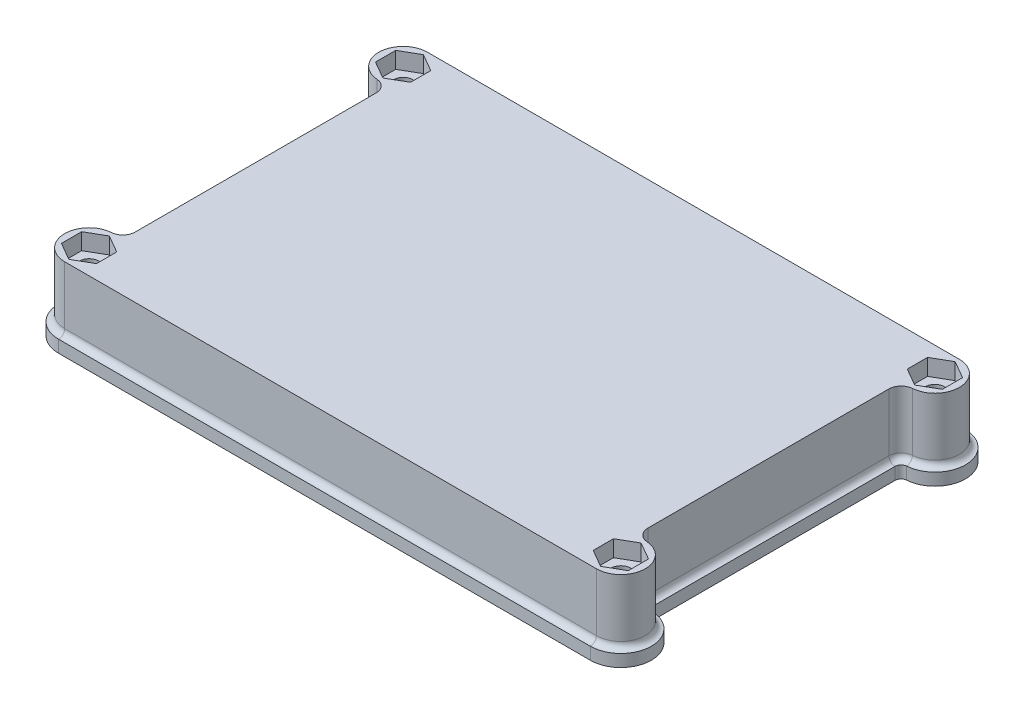
SolidWorks part; units mm, degrees
ref_plane "Спереди" through (0, 0, 0) normal (0, 0, 1) x (1, 0, 0)
ref_plane "Сверху" through (0, 0, 0) normal (0, 1, 0) x (1, 0, 0)
ref_plane "Справа" through (0, 0, 0) normal (1, 0, 0) x (0, 0, -1)
sketch "Эскиз1" plane through (0, 0, 0) normal (0, 1, 0) x (1, 0, 0)
  line L0 (38.2426, -23.75) -> (38.2426, 23.75)
  line L1 (35.2426, -26.75) -> (-36.8302, -26.75)
  line L2 (-42.8302, 19.7659) -> (-42.8302, -19.7659)
  line L3 (41.2426, 19.7659) -> (41.2426, -19.7659)
  line L5 (-39.8302, 23.75) -> (-39.8302, -23.75)
  line L6 (35.2426, 26.75) -> (-36.8302, 26.75)
  line L7 (-44.3938, -29.75) -> (42.8062, -29.75)
  line L10 (42.8062, 29.75) -> (-44.3938, 29.75)
  line L11 (-42.7938, 29.75) -> (41.2062, 29.75)
  line L12 (-42.7938, 0) -> (41.2062, 0) construction
  arc A0 (38.2426, 23.75) -> (35.2426, 26.75) centre (35.2426, 23.75) ccw
  arc A1 (-36.8302, -26.75) -> (-39.8302, -23.75) centre (-36.8302, -23.75) cw
  arc A2 (38.2426, -23.75) -> (35.2426, -26.75) centre (35.2426, -23.75) cw
  arc A3 (-36.8302, 26.75) -> (-39.8302, 23.75) centre (-36.8302, 23.75) ccw
  circle A4 centre (-44.3938, -25.75) radius 1.6
  arc A5 (-44.6847, -21.7606) -> (-44.3938, -29.75) centre (-44.3938, -25.75) ccw
  arc A6 (-44.6847, -21.7606) -> (-42.8302, -19.7659) centre (-44.8302, -19.7659) ccw
  circle A7 centre (-44.3938, 25.75) radius 1.6
  circle A8 centre (42.8062, 25.75) radius 1.6
  circle A9 centre (42.8062, -25.75) radius 1.6
  arc A10 (42.8062, -29.75) -> (43.0971, -21.7606) centre (42.8062, -25.75) ccw
  arc A11 (41.2426, -19.7659) -> (43.0971, -21.7606) centre (43.2426, -19.7659) ccw
  arc A12 (43.0971, 21.7606) -> (41.2426, 19.7659) centre (43.2426, 19.7659) ccw
  arc A13 (43.0971, 21.7606) -> (42.8062, 29.75) centre (42.8062, 25.75) ccw
  arc A14 (-42.8302, 19.7659) -> (-44.6847, 21.7606) centre (-44.8302, 19.7659) ccw
  arc A15 (-44.3938, 29.75) -> (-44.6847, 21.7606) centre (-44.3938, 25.75) ccw
extrude "Бобышка-Вытянуть1" add sketch "Эскиз1" along normal blind 9.5 contours L10 A15 A14 L2 A6 A5 L7 A10 A11 L3 A12 A13 A3 L6 A0 L0 A2 L1 A1 L5 A4 A7 A8 A9 region at (-42.5432, 0, -21.8921)
sketch "Эскиз2" plane through (0, 9.5, 0) normal (0, 1, 0) x (1, 0, 0)
  line L0 (41.2426, 19.7659) -> (41.2426, -19.7659) construction
  line L1 (-44.3938, -29.75) -> (42.8062, -29.75) construction
  line L2 (-42.8302, 19.7659) -> (-42.8302, -19.7659) construction
  line L3 (42.8062, 29.75) -> (-44.3938, 29.75) construction
  line L4 (41.2426, 19.7659) -> (41.2426, -19.7659)
  line L5 (-44.3938, -29.75) -> (42.8062, -29.75)
  line L6 (-42.8302, 19.7659) -> (-42.8302, -19.7659)
  line L7 (42.8062, 29.75) -> (-44.3938, 29.75)
  circle A0 centre (42.8062, 25.75) radius 1.6 construction
  arc A1 (43.0971, 21.7606) -> (42.8062, 29.75) centre (42.8062, 25.75) ccw construction
  arc A2 (43.0971, 21.7606) -> (41.2426, 19.7659) centre (43.2426, 19.7659) ccw construction
  arc A3 (41.2426, -19.7659) -> (43.0971, -21.7606) centre (43.2426, -19.7659) ccw construction
  circle A4 centre (42.8062, -25.75) radius 1.6 construction
  arc A5 (42.8062, -29.75) -> (43.0971, -21.7606) centre (42.8062, -25.75) ccw construction
  circle A6 centre (-44.3938, -25.75) radius 1.6 construction
  arc A7 (-44.6847, -21.7606) -> (-44.3938, -29.75) centre (-44.3938, -25.75) ccw construction
  arc A8 (-44.6847, -21.7606) -> (-42.8302, -19.7659) centre (-44.8302, -19.7659) ccw construction
  circle A9 centre (-44.3938, 25.75) radius 1.6 construction
  arc A10 (-42.8302, 19.7659) -> (-44.6847, 21.7606) centre (-44.8302, 19.7659) ccw construction
  arc A11 (-44.3938, 29.75) -> (-44.6847, 21.7606) centre (-44.3938, 25.75) ccw construction
  circle A12 centre (42.8062, 25.75) radius 1.6
  arc A13 (43.0971, 21.7606) -> (42.8062, 29.75) centre (42.8062, 25.75) ccw
  arc A14 (43.0971, 21.7606) -> (41.2426, 19.7659) centre (43.2426, 19.7659) ccw
  arc A15 (41.2426, -19.7659) -> (43.0971, -21.7606) centre (43.2426, -19.7659) ccw
  circle A16 centre (42.8062, -25.75) radius 1.6
  arc A17 (42.8062, -29.75) -> (43.0971, -21.7606) centre (42.8062, -25.75) ccw
  circle A18 centre (-44.3938, -25.75) radius 1.6
  arc A19 (-44.6847, -21.7606) -> (-44.3938, -29.75) centre (-44.3938, -25.75) ccw
  arc A20 (-44.6847, -21.7606) -> (-42.8302, -19.7659) centre (-44.8302, -19.7659) ccw
  circle A21 centre (-44.3938, 25.75) radius 1.6
  arc A22 (-42.8302, 19.7659) -> (-44.6847, 21.7606) centre (-44.8302, 19.7659) ccw
  arc A23 (-44.3938, 29.75) -> (-44.6847, 21.7606) centre (-44.3938, 25.75) ccw
extrude "Бобышка-Вытянуть2" add sketch "Эскиз2" along normal blind 2
sketch "Эскиз3" plane through (0, 11.5, 0) normal (0, 1, 0) x (1, 0, 0)
  line L0 (-0.7938, 29.75) -> (-0.7938, -29.75) construction
  line L1 (-44.3938, 22.4302) -> (-41.5188, 24.0901)
  line L2 (-41.5188, 24.0901) -> (-41.5188, 27.4099)
  line L3 (-41.5188, 27.4099) -> (-44.3938, 29.0698)
  line L4 (-44.3938, 29.0698) -> (-47.2688, 27.4099)
  line L5 (-47.2688, 27.4099) -> (-47.2688, 24.0901)
  line L6 (-47.2688, 24.0901) -> (-44.3938, 22.4302)
  line L7 (42.8062, 29.75) -> (-44.3938, 29.75) construction
  line L8 (-44.3938, -29.75) -> (42.8062, -29.75) construction
  line L9 (-42.8302, 0) -> (41.2426, 0) construction
  line L10 (-42.8302, 19.7659) -> (-42.8302, -19.7659) construction
  line L11 (41.2426, -19.7659) -> (41.2426, 19.7659) construction
  line L12 (45.6812, 24.0901) -> (42.8062, 22.4302)
  line L13 (45.6812, 27.4099) -> (45.6812, 24.0901)
  line L14 (42.8062, 29.0698) -> (45.6812, 27.4099)
  line L15 (39.9312, 27.4099) -> (42.8062, 29.0698)
  line L16 (39.9312, 24.0901) -> (39.9312, 27.4099)
  line L17 (42.8062, 22.4302) -> (39.9312, 24.0901)
  line L18 (42.8062, -22.4302) -> (39.9312, -24.0901)
  line L19 (39.9312, -24.0901) -> (39.9312, -27.4099)
  line L20 (39.9312, -27.4099) -> (42.8062, -29.0698)
  line L21 (42.8062, -29.0698) -> (45.6812, -27.4099)
  line L22 (45.6812, -27.4099) -> (45.6812, -24.0901)
  line L23 (45.6812, -24.0901) -> (42.8062, -22.4302)
  line L24 (-47.2688, -24.0901) -> (-44.3938, -22.4302)
  line L25 (-47.2688, -27.4099) -> (-47.2688, -24.0901)
  line L26 (-44.3938, -29.0698) -> (-47.2688, -27.4099)
  line L27 (-41.5188, -27.4099) -> (-44.3938, -29.0698)
  line L28 (-41.5188, -24.0901) -> (-41.5188, -27.4099)
  line L29 (-44.3938, -22.4302) -> (-41.5188, -24.0901)
  circle A0 centre (-44.3938, 25.75) radius 2.875 construction
  circle A1 centre (42.8062, 25.75) radius 2.875 construction
  circle A2 centre (42.8062, -25.75) radius 2.875 construction
  circle A3 centre (-44.3938, -25.75) radius 2.875 construction
extrude "Вырез-Вытянуть1" cut sketch "Эскиз3" against normal blind 2.7
sketch "Эскиз4" plane through (0, 0, 0) normal (0, -1, 0) x (1, 0, 0)
  line L0 (-0.7938, 26.75) -> (-0.7938, -26.75) construction
  line L1 (35.2426, 26.75) -> (-36.8302, 26.75) construction
  line L2 (35.2426, -26.75) -> (-36.8302, -26.75) construction
  line L3 (-39.8302, -23.75) -> (-39.8302, 23.75) construction
  line L4 (36.7426, -28.25) -> (-38.3302, -28.25)
  line L5 (39.7426, -25.25) -> (39.7426, 25.25)
  line L6 (36.7426, 28.25) -> (-38.3302, 28.25)
  line L7 (-41.3302, -25.25) -> (-41.3302, 25.25)
  line L8 (39.7426, -28.25) -> (-41.3302, 28.25) construction
  line L9 (39.7426, 28.25) -> (-41.3302, -28.25) construction
  line L10 (35.2426, 26.75) -> (-36.8302, 26.75) construction
  arc A0 (-38.3302, -28.25) -> (-41.3302, -25.25) centre (-38.3302, -25.25) cw
  arc A1 (36.7426, -28.25) -> (39.7426, -25.25) centre (36.7426, -25.25) ccw
  arc A2 (39.7426, 25.25) -> (36.7426, 28.25) centre (36.7426, 25.25) ccw
  arc A3 (-38.3302, 28.25) -> (-41.3302, 25.25) centre (-38.3302, 25.25) ccw
  point P6 (-0.7938, 0)
  point P11 (-41.3302, 0)
  point P14 (-39.8302, 0)
  point P15 (-0.7938, 28.25)
  dimension "D3" = 3
  dimension "D1" = 1.5
  dimension "D2" = 1.5
extrude "Вытянуть-Тонкостенный1" add sketch "Эскиз4" along normal blind 0.5 thin thin type mid plane wall 1
sketch "Эскиз5" plane through (0, 0, 0) normal (0, -1, 0) x (1, 0, 0)
  line L0 (42.8062, -29.75) -> (-44.3938, -29.75) construction
  line L1 (-42.8302, -19.7659) -> (-42.8302, 19.7659) construction
  line L2 (41.2426, -19.7659) -> (41.2426, 19.7659) construction
  line L3 (-44.3938, 29.75) -> (42.8062, 29.75) construction
  line L4 (42.8062, -29.75) -> (-44.3938, -29.75)
  line L5 (-42.8302, -19.7659) -> (-42.8302, 19.7659)
  line L6 (41.2426, -19.7659) -> (41.2426, 19.7659)
  line L7 (-44.3938, 29.75) -> (42.8062, 29.75)
  arc A0 (41.2426, -19.7659) -> (43.0971, -21.7606) centre (43.2426, -19.7659) ccw construction
  arc A1 (42.8062, -29.75) -> (43.0971, -21.7606) centre (42.8062, -25.75) ccw construction
  arc A2 (-44.6847, -21.7606) -> (-44.3938, -29.75) centre (-44.3938, -25.75) ccw construction
  arc A3 (-44.6847, -21.7606) -> (-42.8302, -19.7659) centre (-44.8302, -19.7659) ccw construction
  arc A4 (-42.8302, 19.7659) -> (-44.6847, 21.7606) centre (-44.8302, 19.7659) ccw construction
  arc A5 (-44.3938, 29.75) -> (-44.6847, 21.7606) centre (-44.3938, 25.75) ccw construction
  arc A6 (43.0971, 21.7606) -> (41.2426, 19.7659) centre (43.2426, 19.7659) ccw construction
  arc A7 (43.0971, 21.7606) -> (42.8062, 29.75) centre (42.8062, 25.75) ccw construction
  arc A8 (41.2426, -19.7659) -> (43.0971, -21.7606) centre (43.2426, -19.7659) ccw
  arc A9 (42.8062, -29.75) -> (43.0971, -21.7606) centre (42.8062, -25.75) ccw
  arc A10 (-44.6847, -21.7606) -> (-44.3938, -29.75) centre (-44.3938, -25.75) ccw
  arc A11 (-44.6847, -21.7606) -> (-42.8302, -19.7659) centre (-44.8302, -19.7659) ccw
  arc A12 (-42.8302, 19.7659) -> (-44.6847, 21.7606) centre (-44.8302, 19.7659) ccw
  arc A13 (-44.3938, 29.75) -> (-44.6847, 21.7606) centre (-44.3938, 25.75) ccw
  arc A14 (43.0971, 21.7606) -> (41.2426, 19.7659) centre (43.2426, 19.7659) ccw
  arc A15 (43.0971, 21.7606) -> (42.8062, 29.75) centre (42.8062, 25.75) ccw
extrude "Вытянуть-Тонкостенный2" add sketch "Эскиз5" along normal mid plane 2 thin thin type one direction wall 1
fillet "Скругление1" radius 1 12 edges at (-43.3654, 1, -21.1277) (-42.8302, 1, 0) (-43.3654, 1, 21.1277) (-48.3912, 1, 25.8956) (-0.7938, 1, 29.75) (46.8035, 1, 25.8956) (41.7778, 1, 21.1277) (41.2426, 1, 0) (41.7778, 1, -21.1277) (46.8035, 1, -25.8956) (-0.7938, 1, -29.75) (-48.3912, 1, -25.8956)
sketch "Эскиз6" plane through (0, 0, 0) normal (0, -1, 0) x (1, 0, 0)
  line L0 (-44.3938, -29.75) -> (42.8062, -29.75) construction
  line L1 (-42.8302, -19.7659) -> (-42.8302, 19.7659) construction
  line L2 (42.8062, 29.75) -> (-44.3938, 29.75) construction
  line L3 (41.2426, -19.7659) -> (41.2426, 19.7659) construction
  line L4 (-44.3938, -29.75) -> (42.8062, -29.75)
  line L5 (-42.8302, -19.7659) -> (-42.8302, 19.7659)
  line L6 (42.8062, 29.75) -> (-44.3938, 29.75)
  line L7 (41.2426, -19.7659) -> (41.2426, 19.7659)
  arc A0 (42.8062, -29.75) -> (43.0971, -21.7606) centre (42.8062, -25.75) ccw construction
  arc A1 (41.2426, -19.7659) -> (43.0971, -21.7606) centre (43.2426, -19.7659) ccw construction
  arc A2 (-44.6847, -21.7606) -> (-44.3938, -29.75) centre (-44.3938, -25.75) ccw construction
  arc A3 (-44.6847, -21.7606) -> (-42.8302, -19.7659) centre (-44.8302, -19.7659) ccw construction
  arc A4 (-42.8302, 19.7659) -> (-44.6847, 21.7606) centre (-44.8302, 19.7659) ccw construction
  arc A5 (-44.3938, 29.75) -> (-44.6847, 21.7606) centre (-44.3938, 25.75) ccw construction
  arc A6 (43.0971, 21.7606) -> (41.2426, 19.7659) centre (43.2426, 19.7659) ccw construction
  arc A7 (43.0971, 21.7606) -> (42.8062, 29.75) centre (42.8062, 25.75) ccw construction
  arc A8 (42.8062, -29.75) -> (43.0971, -21.7606) centre (42.8062, -25.75) ccw
  arc A9 (41.2426, -19.7659) -> (43.0971, -21.7606) centre (43.2426, -19.7659) ccw
  arc A10 (-44.6847, -21.7606) -> (-44.3938, -29.75) centre (-44.3938, -25.75) ccw
  arc A11 (-44.6847, -21.7606) -> (-42.8302, -19.7659) centre (-44.8302, -19.7659) ccw
  arc A12 (-42.8302, 19.7659) -> (-44.6847, 21.7606) centre (-44.8302, 19.7659) ccw
  arc A13 (-44.3938, 29.75) -> (-44.6847, 21.7606) centre (-44.3938, 25.75) ccw
  arc A14 (43.0971, 21.7606) -> (41.2426, 19.7659) centre (43.2426, 19.7659) ccw
  arc A15 (43.0971, 21.7606) -> (42.8062, 29.75) centre (42.8062, 25.75) ccw
extrude "Вырез-Вытянуть-Тонкостенный1" cut sketch "Эскиз6" along normal up to next thin thin type one direction wall 0.15
sketch "Эскиз8" plane through (0, 9.5, 0) normal (0, -1, 0) x (1, 0, 0)
  line L1 (-36.7302, 2.75) -> (-23.7302, 2.75)
  line L2 (-39.7302, -0.25) -> (-39.7302, -13.25)
  line L3 (-36.7302, -16.25) -> (-23.7302, -16.25)
  line L4 (-20.7302, -0.25) -> (-20.7302, -13.25)
  line L5 (-39.7302, 2.75) -> (-20.7302, -16.25) construction
  line L6 (-39.7302, -16.25) -> (-20.7302, 2.75) construction
  line L7 (22.1426, 2.75) -> (35.1426, 2.75)
  line L8 (19.1426, -0.25) -> (19.1426, -13.25)
  line L9 (22.1426, -16.25) -> (35.1426, -16.25)
  line L10 (38.1426, -0.25) -> (38.1426, -13.25)
  line L11 (19.1426, 2.75) -> (38.1426, -16.25) construction
  line L12 (19.1426, -16.25) -> (38.1426, 2.75) construction
  line L14 (31.1426, -9.25) -> (26.1426, -9.25)
  line L15 (31.1426, -9.25) -> (31.1426, -4.25)
  line L16 (31.1426, -4.25) -> (26.1426, -4.25)
  line L17 (26.1426, -9.25) -> (26.1426, -4.25)
  line L18 (31.1426, -9.25) -> (26.1426, -4.25) construction
  line L19 (31.1426, -4.25) -> (26.1426, -9.25) construction
  arc A0 (19.1426, -13.25) -> (22.1426, -16.25) centre (22.1426, -13.25) ccw
  arc A1 (35.1426, -16.25) -> (38.1426, -13.25) centre (35.1426, -13.25) ccw
  arc A2 (35.1426, 2.75) -> (38.1426, -0.25) centre (35.1426, -0.25) cw
  arc A3 (22.1426, 2.75) -> (19.1426, -0.25) centre (22.1426, -0.25) ccw
  arc A4 (-39.7302, -13.25) -> (-36.7302, -16.25) centre (-36.7302, -13.25) ccw
  arc A5 (-23.7302, -16.25) -> (-20.7302, -13.25) centre (-23.7302, -13.25) ccw
  arc A6 (-23.7302, 2.75) -> (-20.7302, -0.25) centre (-23.7302, -0.25) cw
  arc A7 (-36.7302, 2.75) -> (-39.7302, -0.25) centre (-36.7302, -0.25) ccw
  circle A8 centre (-30.2302, -6.75) radius 3
  point P0 (-30.2302, -6.75)
  point P6 (28.6426, -6.75)
  point P39 (28.6426, -6.75)
  dimension "D5" = 3
  dimension "D1" = 19
  dimension "D2" = 19
  dimension "D3" = 19
  dimension "D4" = 19
extrude "Вырез-Вытянуть2" cut sketch "Эскиз8" against normal blind 1.5
sketch "Эскиз10" plane through (0, 9.5, 0) normal (0, -1, 0) x (1, 0, 0)
  line L1 (31.1426, -9.25) -> (26.1426, -9.25)
  line L2 (31.1426, -9.25) -> (31.1426, -4.25)
  line L3 (31.1426, -4.25) -> (26.1426, -4.25)
  line L4 (26.1426, -9.25) -> (26.1426, -4.25)
  line L5 (31.1426, -9.25) -> (26.1426, -4.25) construction
  line L6 (31.1426, -4.25) -> (26.1426, -9.25) construction
  line L7 (30.6426, -8.75) -> (26.6426, -8.75)
  line L8 (30.6426, -8.75) -> (30.6426, -4.75)
  line L9 (30.6426, -4.75) -> (26.6426, -4.75)
  line L10 (26.6426, -8.75) -> (26.6426, -4.75)
  line L11 (30.6426, -8.75) -> (26.6426, -4.75) construction
  line L12 (30.6426, -4.75) -> (26.6426, -8.75) construction
  circle A0 centre (-30.2302, -6.75) radius 3
  circle A1 centre (-30.2302, -6.75) radius 2
  point P4 (28.6426, -6.75)
  point P10 (28.6426, -6.75)
  point P15 (0, 0)
  dimension "D1" = 4
  dimension "D2" = 4
extrude "Бобышка-Вытянуть3" add sketch "Эскиз10" along normal blind 2
